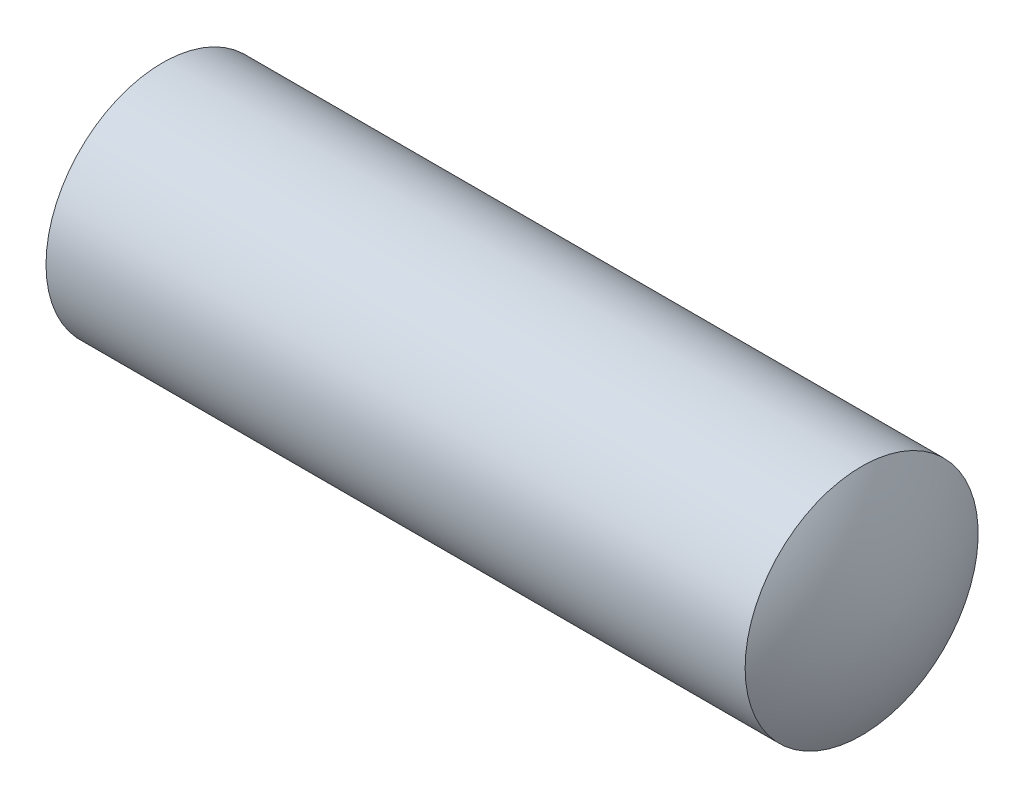
SolidWorks part; units mm, degrees
material "AISI Тип A2 Инструментальная сталь"
ref_plane "Спереди" through (0, 0, 0) normal (0, 0, 1) x (1, 0, 0)
ref_plane "Сверху" through (0, 0, 0) normal (0, 1, 0) x (1, 0, 0)
ref_plane "Справа" through (0, 0, 0) normal (1, 0, 0) x (0, 0, -1)
sketch "Эскиз1" plane through (0, 0, 0) normal (0, 0, 1) x (1, 0, 0)
  line L0 (0, 0) -> (14.3069, 0) construction
  line L1 (0, 0) -> (0, 6.3046) construction
  line L3 (0, 2) -> (12, 2)
  line L6 (12, 2) -> (12, -0.9836) construction
  line L7 (-0.6, 0) -> (12.6, 0)
  arc A1 (0, 2) -> (-0.6, 0) centre (3.3985, -0.1095) ccw
  arc A2 (12, 2) -> (12.6, 0) centre (8.6015, -0.1095) cw
  dimension "D1" = 0.6
  dimension "D4" = 4
  dimension "D6" = 4
  dimension "D2" = 4
  dimension "D3" = 12
  dimension "D5" = 0.6
revolve "Повернуть2" add sketch "Эскиз1" angle 360 about L0
